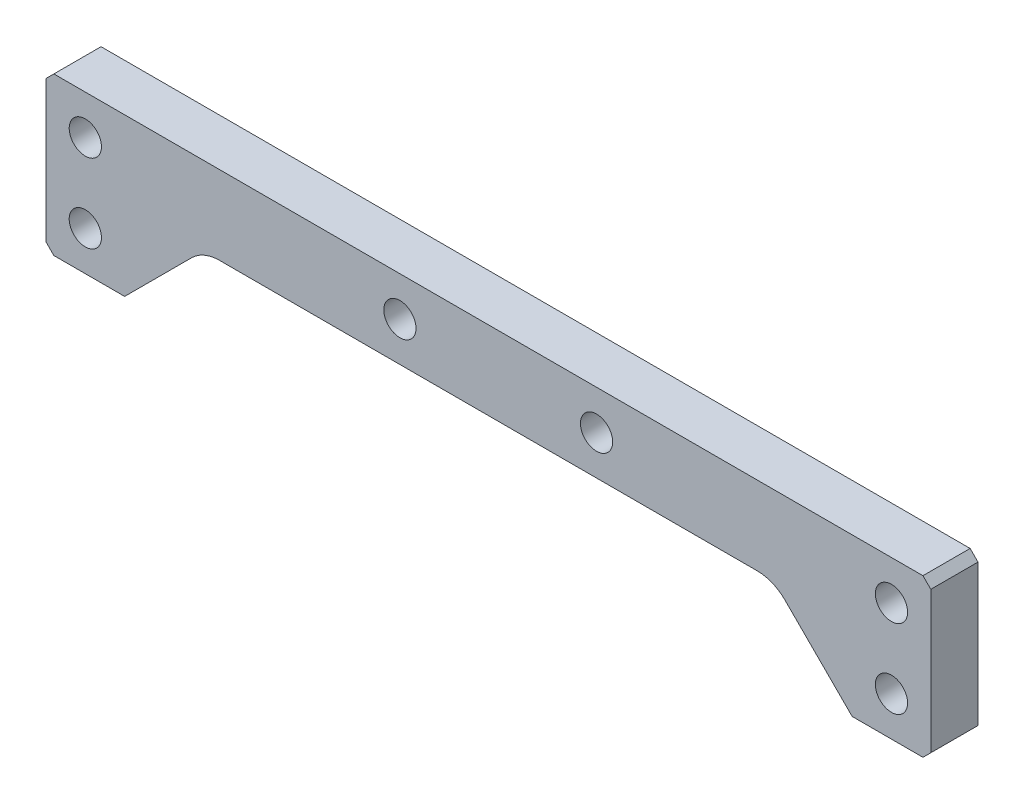
SolidWorks part; units mm, degrees
ref_plane "前视基准面" through (0, 0, 0) normal (0, 0, 1) x (1, 0, 0)
ref_plane "上视基准面" through (0, 0, 0) normal (0, 1, 0) x (1, 0, 0)
ref_plane "右视基准面" through (0, 0, 0) normal (1, 0, 0) x (0, 0, -1)
sketch "草图1" plane through (0, 0, 0) normal (0, 0, 1) x (1, 0, 0)
  line L0 (0, 0) -> (-50, 0) construction
  line L1 (-50, 0) -> (-130, 0) construction
  line L2 (-130, 0) -> (-130, -20) construction
  line L3 (0, 0) -> (75, 0) construction
  line L4 (-140, -10) -> (-120, -10) construction
  line L5 (-140, -10) -> (-140, -30)
  line L6 (-140, -30) -> (-120, -30)
  line L7 (-120, -10) -> (-120, -30)
  line L8 (-140, -10) -> (-120, -30) construction
  line L9 (-140, -30) -> (-120, -10) construction
  line L10 (-140, 10) -> (-120, 10)
  line L11 (-140, 10) -> (-140, -10)
  line L12 (-140, -10) -> (-120, -10) construction
  line L13 (-120, 10) -> (-120, -10) construction
  line L14 (-140, 10) -> (-120, -10) construction
  line L15 (-140, -10) -> (-120, 10) construction
  line L16 (-120, 10) -> (10, 10)
  line L17 (-120, 10) -> (-120, -10) construction
  line L18 (-120, -10) -> (10, -10)
  line L19 (10, 10) -> (10, -10) construction
  line L20 (-55, -10) -> (-55, 10) construction
  line L21 (-120, 0) -> (10, 0) construction
  line L22 (75, 0) -> (75, -20) construction
  line L23 (10, 10) -> (85, 10)
  line L24 (85, 10) -> (85, -30)
  line L25 (85, -30) -> (65, -30)
  line L26 (65, -30) -> (65, -10)
  line L27 (65, -10) -> (10, -10)
  circle A0 centre (0, 0) radius 4.1
  circle A1 centre (-50, 0) radius 4.1
  circle A2 centre (-130, 0) radius 4.1
  circle A3 centre (-130, -20) radius 4.1
  circle A4 centre (75, 0) radius 4.1
  circle A5 centre (75, -20) radius 4.1
  point P262 (-55, 0)
extrude "凸台-拉伸1" add sketch "草图1" along normal blind 12
chamfer "倒角1" distance 20 angle 45 2 edges at (65, -10, 6) (-120, -10, 6)
fillet "圆角1" radius 10 2 edges at (45, -10, 6) (-100, -10, 6)
chamfer "倒角2" distance 2 angle 45 4 edges at (-140, -30, 6) (-140, 10, 6) (85, -30, 6) (85, 10, 6)
